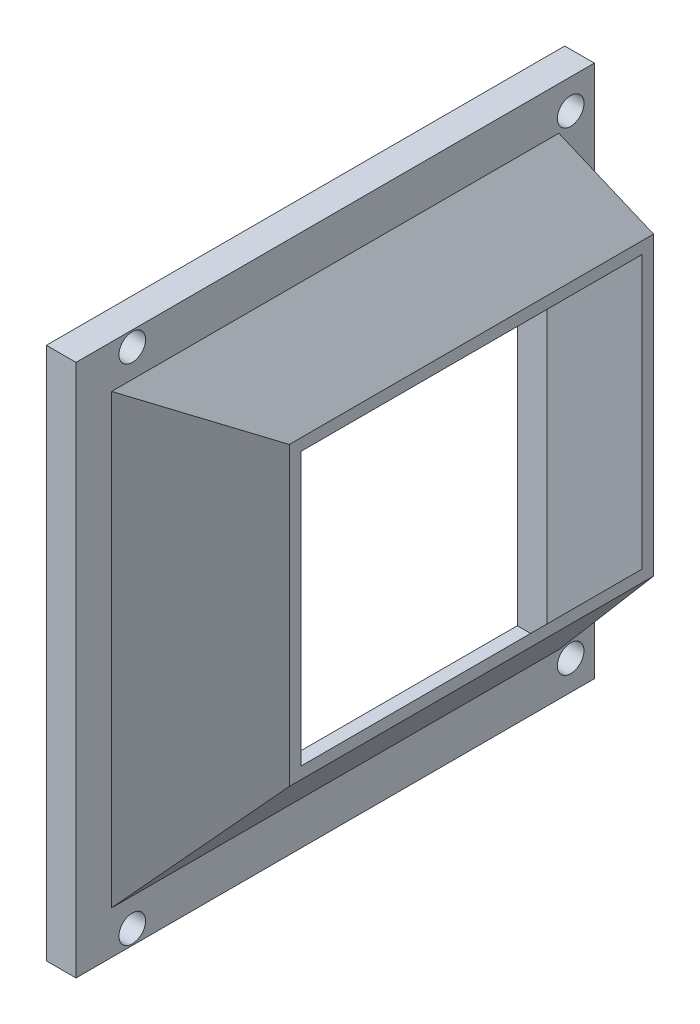
SolidWorks part; units mm, degrees
ref_plane "Front Plane" through (0, 0, 0) normal (0, 0, 1) x (1, 0, 0)
ref_plane "Top Plane" through (0, 0, 0) normal (0, 1, 0) x (1, 0, 0)
ref_plane "Right Plane" through (0, 0, 0) normal (1, 0, 0) x (0, 0, -1)
sketch "Sketch1" plane through (0, 0, 0) normal (1, 0, 0) x (0, 0, -1)
  line L1 (-43.75, -45) -> (43.75, -45)
  line L2 (-43.75, -45) -> (-43.75, 45)
  line L3 (-43.75, 45) -> (43.75, 45)
  line L4 (43.75, -45) -> (43.75, 45)
  line L5 (-43.75, -45) -> (43.75, 45) construction
  line L6 (-43.75, 45) -> (43.75, -45) construction
  line L7 (-35.75, -35.75) -> (35.75, -35.75)
  line L8 (-35.75, -35.75) -> (-35.75, 35.75)
  line L9 (-35.75, 35.75) -> (35.75, 35.75)
  line L10 (35.75, -35.75) -> (35.75, 35.75)
  line L11 (-35.75, -35.75) -> (35.75, 35.75) construction
  line L12 (-35.75, 35.75) -> (35.75, -35.75) construction
  point P0 (0, 0)
  point P6 (0, 0)
  dimension "D1" = 87.5
  dimension "D2" = 90
  dimension "D3" = 71.5
  dimension "D4" = 71.5
extrude "Boss-Extrude1" add sketch "Sketch1" along normal blind 5
hole_wizard "M4 Clearance Hole1" positions "Sketch2" profile "Sketch3" hole size "M4" standard "ANSI Metric" end condition through all
sketch "Sketch2" plane through (5, 0, 0) normal (1, 0, 0) x (0, 0, -1)
  line L0 (43.75, -45) -> (43.75, 45) construction
  line L1 (43.75, 45) -> (-43.75, 45) construction
  line L2 (-43.75, 45) -> (-43.75, -45) construction
  point P0 (-34.25, 42.5)
  point P2 (39.75, 40)
  dimension "D1" = 4
  dimension "D2" = 5
  dimension "D3" = 9.5
  dimension "D4" = 2.5
sketch "Sketch3" plane through (5, 42.5, 34.25) normal (0, 1, 0) x (0, 0, -1)
  line L0 (0, 0) -> (0, 5)
  line L1 (0, 5) -> (2.25, 5)
  line L2 (2.25, 5) -> (2.25, 0)
  line L5 (2.25, 0) -> (0, 0)
  line L11 (0, -6.35) -> (0, 107.95) construction
  dimension "Thru Hole Dia." = 4.5
  dimension "Thru Hole Depth" = 5
mirror "Mirror1" about plane through (0, 0, 0) normal (0, 1, 0) of "M4 Clearance Hole1"
sketch "Sketch4" plane through (0, 45, 0) normal (0, 1, 0) x (1, 0, 0)
  line L0 (5, 35.75) -> (15, 41.75)
  line L1 (5, 43.75) -> (5, -43.75) construction
  line L2 (5, -35.75) -> (15, -15.75)
  line L4 (15, -15.75) -> (15, -17.75)
  line L5 (15, -17.75) -> (5, -37.75)
  line L6 (15, 41.75) -> (15, 43.75)
  line L7 (15, 43.75) -> (5, 37.75)
  line L8 (5, -37.75) -> (5, -35.75)
  line L9 (5, 35.75) -> (5, 37.75)
  point P7 (0, 0)
  point P13 (0, 0)
  dimension "D1" = 20
  dimension "D2" = 10
  dimension "D3" = 10
  dimension "D4" = 2
  dimension "D5" = 2
  dimension "D6" = 8
  dimension "D7" = 8
extrude "Boss-Extrude2" add sketch "Sketch4" against normal up to vertex (90 mm away) up to point (5, -45, 43.75)
sketch "Sketch5" plane through (0, 0, -43.75) normal (0, 0, -1) x (-1, 0, 0)
  line L0 (-5, 35.75) -> (-15, 23)
  line L1 (-5, -45) -> (-5, 45) construction
  line L2 (-15, 23) -> (-15, 25)
  line L3 (-15, 25) -> (-5, 37.75)
  line L4 (-5, 45) -> (0, 45) construction
  line L5 (-5, -37.75) -> (-15, -25)
  line L6 (-15, -25) -> (-15, -23)
  line L7 (-15, -23) -> (-5, -35.75)
  line L8 (-5, 37.75) -> (-5, 35.75)
  line L9 (-5, -35.75) -> (-5, -37.75)
  dimension "D1" = 2
  dimension "D2" = 10
  dimension "D3" = 20
  dimension "D4" = 9.25
  dimension "D5" = 2
  dimension "D6" = 10
  dimension "D7" = 20
  dimension "D8" = 9.25
extrude "Boss-Extrude3" add sketch "Sketch5" against normal up to vertex (87.5 mm away) up to point (0, -45, 43.75)
sketch "Sketch6" plane through (0, 0, -43.75) normal (0, 0, -1) x (-1, 0, 0)
  line L0 (-5, 45) -> (-15, 45)
  line L1 (-15, 45) -> (-15, 25)
  line L2 (-15, 25) -> (-5, 37.75)
  line L3 (-5, 37.75) -> (-5, 45)
  line L4 (-15, -25) -> (-15, -45)
  line L5 (-15, -45) -> (-5, -45)
  line L6 (-5, -45) -> (-5, -37.75)
  line L7 (-5, -37.75) -> (-15, -25)
extrude "Cut-Extrude1" cut sketch "Sketch6" against normal up to vertex (87.5 mm away) up to point (0, 45, 43.75)
sketch "Sketch7" plane through (0, 45, 0) normal (0, 1, 0) x (1, 0, 0)
  line L0 (5, -43.75) -> (15, -43.75)
  line L2 (15, -43.75) -> (15, -17.75)
  line L3 (5, -43.75) -> (5, -37.75)
  line L4 (5, 43.75) -> (5, -43.75) construction
  line L5 (5, -37.75) -> (15, -17.75)
  line L6 (5, 43.75) -> (15, 43.75)
  line L7 (15, 43.75) -> (5, 37.75)
  line L8 (5, 43.75) -> (5, 37.75)
  dimension "D1" = 26
  dimension "D2" = 10
  dimension "D3" = 6
  dimension "D4" = 10
  dimension "D5" = 6
extrude "Cut-Extrude2" cut sketch "Sketch7" against normal up to vertex (90 mm away) up to point (0, -45, 43.75)
